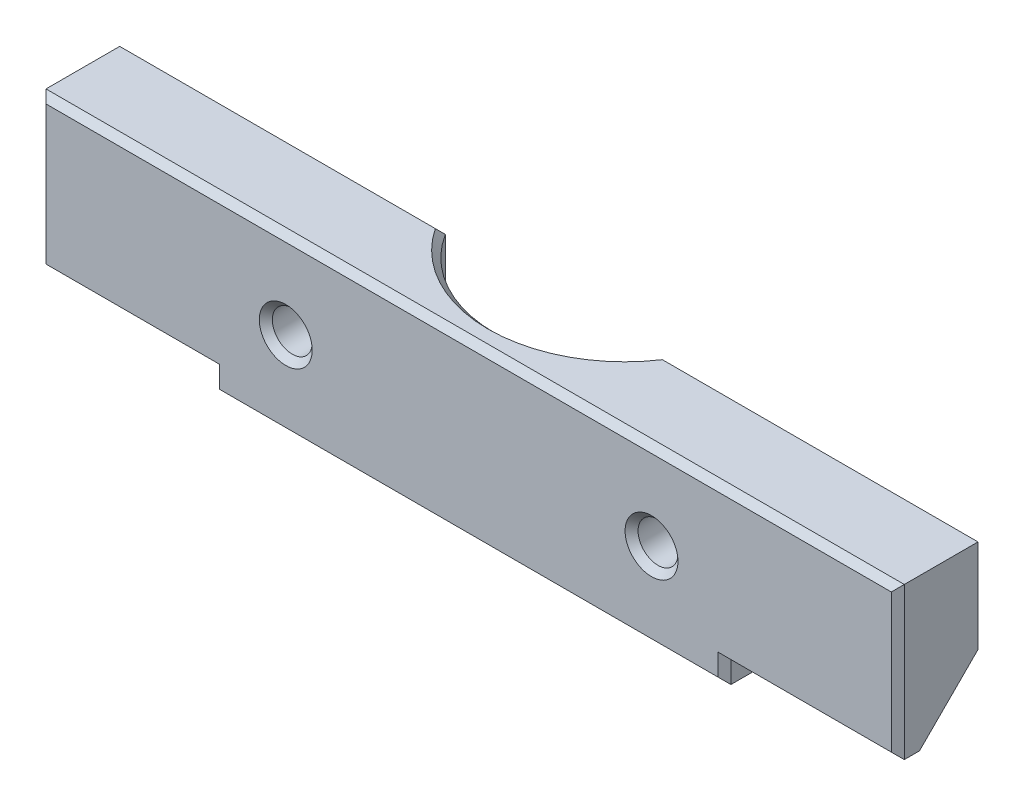
SolidWorks part; units mm, degrees
ref_plane "Front" through (0, 0, 0) normal (0, 0, 1) x (1, 0, 0)
ref_plane "Top" through (0, 0, 0) normal (0, 1, 0) x (1, 0, 0)
ref_plane "Right" through (0, 0, 0) normal (1, 0, 0) x (0, 0, -1)
sketch "Skizze1" plane through (0, 0, 0) normal (0, 0, 1) x (1, 0, 0)
  line L0 (0, 0) -> (0, 36.2286) construction
  line L1 (29.5, 0) -> (-29.5, 0)
  line L2 (-29.5, 0) -> (-29.5, 20)
  line L3 (-29.5, 20) -> (29.5, 20)
  line L4 (29.5, 0) -> (29.5, 20)
  point P7 (0, 20)
  dimension "D1" = 20
  dimension "D2" = 59
extrude "Aufsatz-Linear austragen1" add sketch "Skizze1" along normal blind 10
sketch "Skizze2" plane through (-29.5, 0, 0) normal (-1, 0, 0) x (0, 0, 1)
  line L0 (10, 0) -> (0, 10)
  line L1 (0, 20) -> (0, 0) construction
  line L2 (0, 10) -> (0, 20)
  line L3 (0, 20) -> (10, 20)
  line L4 (10, 20) -> (10, 0)
extrude "Aufsatz-Linear austragen2" add sketch "Skizze2" along normal blind 20
mirror "Spiegeln1" about plane through (0, 0, 0) normal (1, 0, 0) of "Aufsatz-Linear austragen2"
sketch "Skizze3" plane through (0, 0, 0) normal (0, -1, 0) x (1, 0, 0)
  line L0 (0, 0) -> (0, -17.264) construction
  circle A0 centre (0, -8) radius 15
  dimension "D1" = 30
extrude "Schnitt-Linear austragen1" cut sketch "Skizze3" against normal blind 20
sketch "Skizze4" plane through (0, 0, 0) normal (0, 0, -1) x (-1, 0, 0)
  line L0 (-12.6886, 10) -> (-29.5, 10) construction
  line L4 (-12.6886, 0) -> (-12.6886, 20) construction
  line L5 (0, 0) -> (0, 20) construction
  line L6 (-12.6886, 0) -> (12.6886, 0) construction
  line L7 (12.6886, 20) -> (-12.6886, 20) construction
  circle A1 centre (-21.0943, 10) radius 2.3
  circle A2 centre (21.0943, 10) radius 2.3
  dimension "D1" = 4.6
extrude "Schnitt-Linear austragen2" cut sketch "Skizze4" against normal blind 20
sketch "Skizze5" plane through (0, 0, 0) normal (0, 0, -1) x (-1, 0, 0)
  circle A0 centre (-21.0943, 10) radius 3.75
  circle A1 centre (21.0943, 10) radius 3.75
  dimension "D1" = 7.5
extrude "Schnitt-Linear austragen3" cut sketch "Skizze5" against normal blind 3
sketch "Skizze6" plane through (-49.5, 0, 0) normal (-1, 0, 0) x (0, 0, 1)
  line L0 (10, 2.5) -> (4.8526, 2.5)
  line L1 (10, 0) -> (10, 20) construction
  line L2 (4.8526, 2.5) -> (4.8526, -2.6686)
  line L3 (4.8526, -2.6686) -> (13.5868, -2.7881)
  line L4 (13.5868, -2.7881) -> (13.5868, 2.151)
  line L5 (13.5868, 2.151) -> (10, 2.5)
  dimension "D1" = 2.5
extrude "Schnitt-Linear austragen4" cut sketch "Skizze6" against normal blind 20
mirror "Spiegeln3" about plane through (0, 0, 0) normal (1, 0, 0) of "Schnitt-Linear austragen4"
chamfer "Fase3" distance 0.75 angle 45 22 edges at (0, 0, 10) (-29.5, 1.25, 10) (-39.5, 2.5, 10) (-49.5, 11.25, 10) (0, 20, 10) (49.5, 11.25, 10) (39.5, 2.5, 10) (29.5, 1.25, 10) (-18.7943, 10, 10) (23.3943, 10, 10) (-24.8443, 10, 0) (17.3443, 10, 0) (49.5, 15, 0) (31.0943, 20, 0) (0, 20, 7) (-31.0943, 20, 0) (-49.5, 15, 0) (29.5, 5, 0) (21.0943, 0, 0) (0, 0, 7) (-29.5, 5, 0) (-21.0943, 0, 0)
